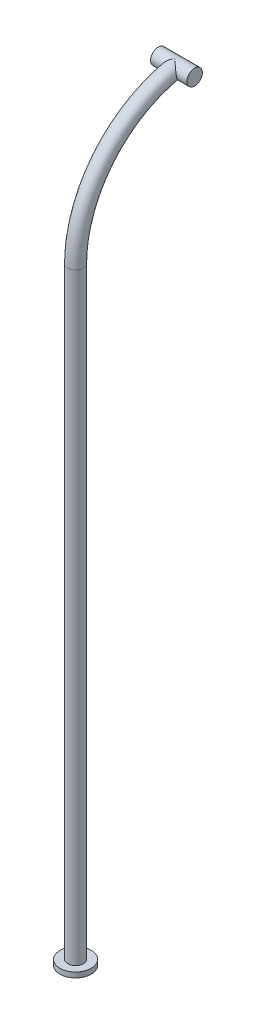
SolidWorks part; units mm, degrees
material "Nylon 101"
ref_plane "Front Plane" through (0, 0, 0) normal (0, 0, 1) x (1, 0, 0)
ref_plane "Top Plane" through (0, 0, 0) normal (0, 1, 0) x (1, 0, 0)
ref_plane "Right Plane" through (0, 0, 0) normal (1, 0, 0) x (0, 0, -1)
sketch "Sketch1" plane through (0, 0, 0) normal (0, 1, 0) x (1, 0, 0)
  circle A0 centre (0, 0) radius 1.5
extrude "Boss-Extrude1" add sketch "Sketch1" along normal blind 116
sketch "Sketch4" plane through (0, 0, 0) normal (0, -1, 0) x (1, 0, 0)
  circle A0 centre (0, 0) radius 3
extrude "Boss-Extrude4" add sketch "Sketch4" along normal blind 1
sketch "Sketch7" plane through (0, 116, 0) normal (0, 1, 0) x (1, 0, 0)
  line L0 (0, 0) -> (0, 44.3626) construction
  line L1 (0, 44.3626) -> (0, 23.5) construction
  line L2 (0, 23.5) -> (-42.5101, 23.5) construction
  line L3 (-42.5101, 23.5) -> (39.1951, 23.5) construction
  circle A0 centre (0, 0) radius 1.5
  dimension "D1" = 23.5
revolve "Revolve1" add sketch "Sketch7" angle 80 about L3 reverse direction yes
sketch "Sketch8" plane through (0, 0, 0) normal (1, 0, 0) x (0, 0, -1)
  line L0 (19.6797, 137.6658) -> (19.1588, 140.6202) construction
  circle A0 centre (19.4193, 139.143) radius 1.5
extrude "Boss-Extrude5" add sketch "Sketch8" along normal blind 3.5 and the other way blind 3.5
equation "\"4.5.00mm\"=10"
